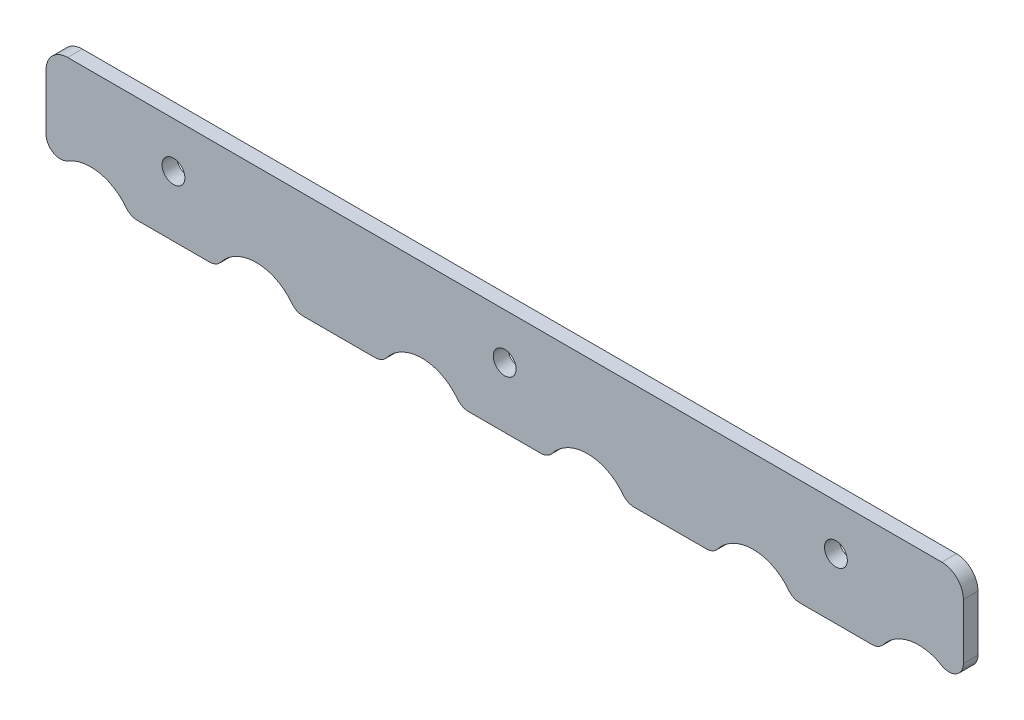
SolidWorks part; units mm, degrees
material "3003-H14"
ref_plane "X-Y Datum" through (0, 0, 0) normal (0, 0, 1) x (1, 0, 0)
ref_plane "X-Z Datum" through (0, 0, 0) normal (0, 1, 0) x (1, 0, 0)
ref_plane "Y-Z Datum" through (0, 0, 0) normal (1, 0, 0) x (0, 0, -1)
sketch "Sketch3" plane through (0, 0, 0) normal (0, 0, 1) x (1, 0, 0)
  line L1 (0, 0) -> (156.4633, 0) construction
  line L2 (0, 0) -> (0, 56.3098) construction
  line L3 (0, 56.3098) -> (156.4633, 56.3098) construction
  line L4 (156.4633, 0) -> (156.4633, 56.3098) construction
  line L5 (4.575, 10.775) -> (4.575, 28.535)
  line L6 (4.575, 28.535) -> (131.975, 28.535)
  line L7 (131.975, 28.535) -> (131.975, 10.775)
  line L9 (4.575, 13.775) -> (131.975, 13.775)
  line L10 (10.775, 10.775) -> (33.775, 10.775) construction
  line L11 (56.775, 10.775) -> (33.775, 10.775) construction
  line L48 (56.775, 10.775) -> (125.775, 10.775) construction
  circle A0 centre (10.775, 10.775) radius 10.775 construction
  circle A1 centre (33.775, 10.775) radius 10.775 construction
  circle A5 centre (56.775, 10.775) radius 10.775 construction
  circle A6 centre (10.775, 10.775) radius 4.7 construction
  circle A7 centre (33.775, 10.775) radius 4.7 construction
  circle A8 centre (56.775, 10.775) radius 4.7 construction
  circle A12 centre (79.775, 10.775) radius 10.775 construction
  circle A13 centre (79.775, 10.775) radius 4.7 construction
  circle A14 centre (102.775, 10.775) radius 10.775 construction
  circle A15 centre (102.775, 10.775) radius 4.7 construction
  circle A16 centre (125.775, 10.775) radius 10.775 construction
  circle A17 centre (125.775, 10.775) radius 4.7 construction
  circle A18 centre (125.775, 10.775) radius 10.775 construction
  circle A19 centre (102.775, 10.775) radius 10.775 construction
  circle A20 centre (79.775, 10.775) radius 10.775 construction
  circle A25 centre (10.775, 10.775) radius 6.2
  circle A26 centre (33.775, 10.775) radius 6.2
  circle A27 centre (56.775, 10.775) radius 6.2
  circle A28 centre (79.775, 10.775) radius 6.2
  circle A29 centre (102.775, 10.775) radius 6.2
  circle A30 centre (125.775, 10.775) radius 6.2
  dimension "D1" = 21.55
  dimension "D9" = 9.4
  dimension "D2" = 23
  dimension "D3" = 1.5
  dimension "D4" = 14.76
  dimension "D8" = 23
  dimension "D11" = 23
  dimension "D5" = 3
  dimension "D10" = 4
  dimension "D7" = 5
extrude "Boss-Extrude1" add sketch "Sketch3" along normal blind 2.032 contours A30 L9 L7 L6 L5 A25 A26 A27 A28 A29 | A25 L9 L5 | A30 L7 L9 region at (4.8045, 13.0347, 0) region at (68.275, 21.6738, 0) region at (131.7455, 13.0347, 0)
fillet "Fillet1" radius 3 2 edges at (4.575, 28.535, 1.016) (131.975, 28.535, 1.016)
fillet "Fillet2" radius 2 12 edges at (131.975, 10.775, 1.016) (120.3491, 13.775, 1.016) (108.2009, 13.775, 1.016) (97.3491, 13.775, 1.016) (85.2009, 13.775, 1.016) (74.3491, 13.775, 1.016) (62.2009, 13.775, 1.016) (51.3491, 13.775, 1.016) (39.2009, 13.775, 1.016) (28.3491, 13.775, 1.016) (16.2009, 13.775, 1.016) (4.575, 10.775, 1.016)
sketch "Sketch4" plane through (0, 0, 0) normal (0, 0, -1) x (-1, 0, 0)
  line L0 (-131.975, 22.185) -> (-4.575, 22.185) construction
  line L1 (-131.975, 25.535) -> (-131.975, 17.8177) construction
  line L2 (-4.575, 17.8177) -> (-4.575, 25.535) construction
  line L3 (-7.575, 28.535) -> (-128.975, 28.535) construction
  line L4 (-68.275, 28.535) -> (-68.275, 13.775) construction
  line L5 (-63.2742, 13.775) -> (-73.2758, 13.775) construction
  line L6 (-68.275, 22.185) -> (-4.575, 22.185) construction
  line L7 (-22.275, 13.775) -> (-22.275, 28.535) construction
  line L8 (-17.2742, 13.775) -> (-27.2758, 13.775) construction
  line L9 (-114.275, 13.775) -> (-114.275, 28.535) construction
  line L10 (-109.2742, 13.775) -> (-119.2758, 13.775) construction
  circle A0 centre (-22.275, 22.185) radius 1.5875
  circle A1 centre (-68.275, 22.185) radius 1.5875
  circle A3 centre (-114.275, 22.185) radius 1.5875
  point P30 (-68.275, 22.185)
  dimension "D1" = 3.175
  dimension "D2" = 6.35
extrude "Cut-Extrude1" cut sketch "Sketch4" against normal through all
